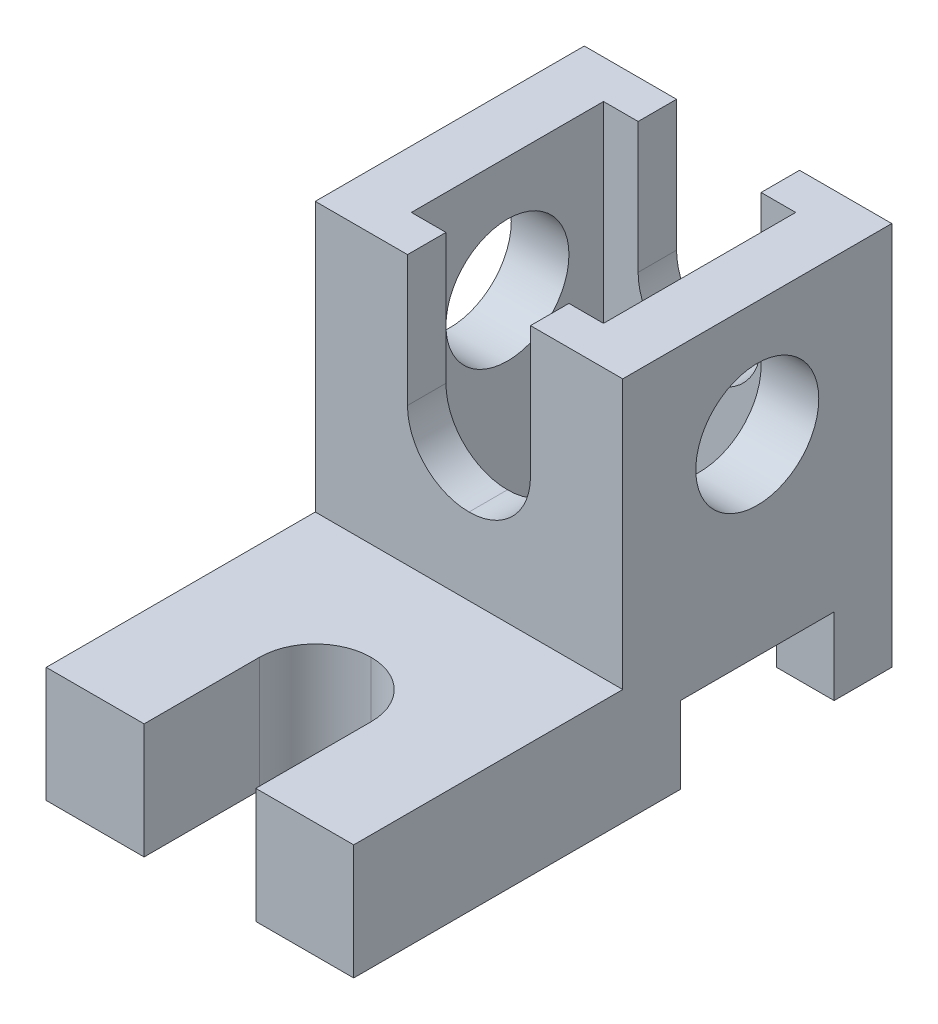
SolidWorks part; units mm, degrees
ref_plane "Front Plane" through (0, 0, 0) normal (0, 0, 1) x (1, 0, 0)
ref_plane "Top Plane" through (0, 0, 0) normal (0, 1, 0) x (1, 0, 0)
ref_plane "Right Plane" through (0, 0, 0) normal (1, 0, 0) x (0, 0, -1)
sketch "Sketch1" plane through (0, 0, 0) normal (1, 0, 0) x (0, 0, -1)
  line L0 (-105, 0) -> (-20, 0)
  line L1 (-20, 0) -> (-20, 20)
  line L2 (-20, 20) -> (20, 20)
  line L3 (20, 20) -> (20, 0)
  line L4 (20, 0) -> (35, 0)
  line L5 (35, 0) -> (35, 100)
  line L6 (35, 100) -> (-35, 100)
  line L7 (-35, 100) -> (-35, 30)
  line L8 (-35, 30) -> (-105, 30)
  line L9 (-105, 30) -> (-105, 0)
  line L10 (0, 0) -> (0, 139.1977) construction
  circle A0 centre (0, 70) radius 16
  dimension "D7" = 32
  dimension "D1" = 140
  dimension "D2" = 40
  dimension "D3" = 30
  dimension "D4" = 100
  dimension "D5" = 20
  dimension "D6" = 70
  dimension "D8" = 70
extrude "Boss-Extrude1" add sketch "Sketch1" along normal blind 40 and the other way blind 40
sketch "Sketch2" plane through (0, 100, 0) normal (0, 1, 0) x (1, 0, 0)
  line L1 (-25, 25) -> (25, 25)
  line L2 (-25, 25) -> (-25, -25)
  line L3 (-25, -25) -> (25, -25)
  line L4 (25, 25) -> (25, -25)
  line L5 (-25, 25) -> (25, -25) construction
  line L6 (-25, -25) -> (25, 25) construction
  point P0 (0, 0)
  dimension "D1" = 50
  dimension "D2" = 50
extrude "Cut-Extrude1" cut sketch "Sketch2" against normal through all
sketch "Sketch3" plane through (0, 0, 35) normal (0, 0, 1) x (1, 0, 0)
  line L0 (-40, 100) -> (40, 100) construction
  line L1 (-16, 100) -> (16, 100)
  line L2 (-16, 100) -> (-16, 50)
  line L3 (-16, 50) -> (16, 50)
  line L4 (16, 100) -> (16, 50)
  line L5 (0, 0) -> (0, 119.4182) construction
  line L6 (-40, 0) -> (40, 0) construction
  dimension "D1" = 50
  dimension "D2" = 32
extrude "Cut-Extrude2" cut sketch "Sketch3" against normal through all
fillet "Fillet1" radius 16 4 edges at (-16, 50, -30) (16, 50, -30) (16, 50, 30) (-16, 50, 30)
sketch "Sketch4" plane through (0, 30, 0) normal (0, 1, 0) x (1, 0, 0)
  line L0 (-40, -105) -> (40, -105) construction
  line L1 (-14.53, -105) -> (14.53, -105)
  line L2 (-14.53, -105) -> (-14.53, -60.47)
  line L3 (-14.53, -60.47) -> (14.53, -60.47)
  line L4 (14.53, -105) -> (14.53, -60.47)
  line L5 (0, 0) -> (0, -118.7737) construction
  dimension "D1" = 44.53
  dimension "D2" = 29.06
extrude "Cut-Extrude3" cut sketch "Sketch4" against normal through all
fillet "Fillet2" radius 14.53 2 edges at (14.53, 15, 60.47) (-14.53, 15, 60.47)
